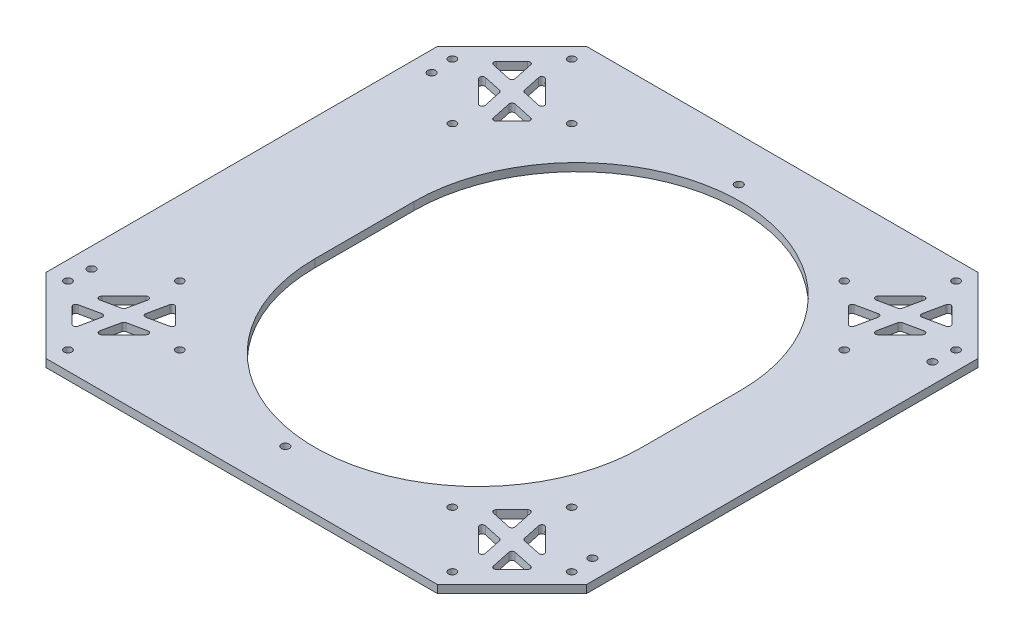
SolidWorks part; units mm, degrees
material "Thornel Mat VMA"
ref_plane "前视基准面" through (0, 0, 0) normal (0, 0, 1) x (1, 0, 0)
ref_plane "上视基准面" through (0, 0, 0) normal (0, 1, 0) x (1, 0, 0)
ref_plane "右视基准面" through (0, 0, 0) normal (1, 0, 0) x (0, 0, -1)
sketch "草图1" plane through (0, 0, 0) normal (0, 1, 0) x (1, 0, 0)
  line L0 (-74.2462, 102.5305) -> (-102.5305, 74.2462)
  line L1 (74.2462, 102.5305) -> (-74.2462, 102.5305)
  line L2 (102.5305, 74.2462) -> (102.5305, -74.2462)
  line L3 (74.2462, -102.5305) -> (-74.2462, -102.5305)
  line L4 (-102.5305, 74.2462) -> (-102.5305, -74.2462)
  line L5 (102.5305, 102.5305) -> (-102.5305, -102.5305) construction
  line L6 (102.5305, -102.5305) -> (-102.5305, 102.5305) construction
  line L7 (102.5305, -74.2462) -> (74.2462, -102.5305)
  line L8 (-102.5305, -74.2462) -> (-74.2462, -102.5305)
  line L9 (74.2462, 102.5305) -> (102.5305, 74.2462)
  line L10 (-102.5305, 102.5305) -> (-102.5305, -102.5305) construction
  line L11 (-102.5305, -102.5305) -> (102.5305, -102.5305) construction
  line L12 (102.5305, -102.5305) -> (102.5305, 102.5305) construction
  line L13 (102.5305, 102.5305) -> (-102.5305, 102.5305) construction
  point P0 (0, 0)
  dimension "D1" = 250
  dimension "D2" = 40
extrude "凸台-拉伸1" add sketch "草图1" along normal blind 3
hole_wizard "孔1" positions "草图4" profile "草图5" legacy
sketch "草图4" plane through (0, 3, 0) normal (0, 1, 0) x (1, 0, 0)
  point P0 (-95.5397, 72.9159)
  point P3 (-74.3265, 51.7027)
  point P6 (-51.6991, 74.3301)
  point P9 (-72.9123, 95.5433)
  point P16 (72.9159, 95.5397)
  point P17 (51.7027, 74.3265)
  point P18 (74.3301, 51.6991)
  point P19 (95.5433, 72.9123)
  point P20 (95.5397, -72.9159)
  point P21 (74.3265, -51.7027)
  point P22 (51.6991, -74.3301)
  point P23 (72.9123, -95.5433)
  point P24 (-72.9159, -95.5397)
  point P25 (-51.7027, -74.3265)
  point P26 (-74.3301, -51.6991)
  point P27 (-95.5433, -72.9123)
  dimension "D1" = 4
sketch "草图5" plane through (-95.5397, 3, -72.9159) normal (1, 0, 0) x (0, 0, 1)
  line L0 (0, 0) -> (0, 100)
  line L1 (0, 100) -> (1.45, 100)
  line L2 (1.45, 100) -> (1.45, 0)
  line L3 (1.45, 0) -> (0, 0)
  line L4 (0, 110) -> (0, -10) construction
  dimension "直径" = 2.9
  dimension "深度" = 100
sketch "草图7" plane through (0, 3, 0) normal (0, 1, 0) x (1, 0, 0)
  line L0 (-95.5397, 72.9159) -> (-51.6991, 74.3301) construction
  line L1 (-86.393, 80.4842) -> (-80.4806, 86.3966)
  line L2 (-84.1601, 71.4358) -> (-75.8066, 63.0823)
  line L3 (-71.4322, 84.1637) -> (-63.0787, 75.8102)
  line L4 (-66.7582, 60.8494) -> (-60.8458, 66.7618)
  line L5 (-89.8008, 77.0764) -> (-57.438, 70.1696) construction
  line L6 (-77.0728, 89.8044) -> (-70.166, 57.4416) construction
  line L7 (-49.2242, 67.6126) -> (-79.6109, 97.9993) construction
  line L8 (-74.2462, 102.5305) -> (-102.5305, 74.2462) construction
  line L9 (-85.8946, 78.7991) -> (-78.378, 77.1949)
  line L10 (-83.2443, 73.1208) -> (-76.36, 71.6516)
  line L11 (-87.6941, 79.1831) -> (-89.8008, 77.0764) construction
  line L12 (-89.8008, 77.0764) -> (-86.5509, 73.8265) construction
  line L13 (-60.6879, 73.4195) -> (-57.438, 70.1696) construction
  line L14 (-57.438, 70.1696) -> (-59.5447, 68.0629) construction
  line L15 (-67.4604, 74.8648) -> (-68.504, 69.975) construction
  line L16 (-73.6194, 73.623) -> (-67.2554, 79.987) construction
  line L17 (-74.1216, 63.9981) -> (-75.5908, 70.8824)
  line L18 (-68.4433, 61.3478) -> (-70.0475, 68.8644)
  line L19 (-70.8788, 75.5944) -> (-63.9945, 74.1252)
  line L20 (-77.1913, 78.3816) -> (-78.7955, 85.8982)
  line L21 (-68.8608, 70.0511) -> (-61.3442, 68.4469)
  line L22 (-71.648, 76.3636) -> (-73.1172, 83.2479)
  line L23 (80.4842, 86.393) -> (86.3966, 80.4806)
  line L24 (71.4358, 84.1601) -> (63.0823, 75.8066)
  line L25 (84.1637, 71.4322) -> (75.8102, 63.0787)
  line L26 (60.8494, 66.7582) -> (66.7618, 60.8458)
  line L27 (78.7991, 85.8946) -> (77.1949, 78.378)
  line L28 (73.1208, 83.2443) -> (71.6516, 76.36)
  line L29 (63.9981, 74.1216) -> (70.8824, 75.5908)
  line L30 (61.3478, 68.4433) -> (68.8644, 70.0475)
  line L31 (75.5944, 70.8788) -> (74.1252, 63.9945)
  line L32 (78.3816, 77.1913) -> (85.8982, 78.7955)
  line L33 (70.0511, 68.8608) -> (68.4469, 61.3442)
  line L34 (76.3636, 71.648) -> (83.2479, 73.1172)
  line L35 (72.9159, 95.5397) -> (74.3301, 51.6991) construction
  line L36 (77.0764, 89.8008) -> (70.1696, 57.438) construction
  line L37 (89.8044, 77.0728) -> (57.4416, 70.166) construction
  line L38 (79.1831, 87.6941) -> (77.0764, 89.8008) construction
  line L39 (77.0764, 89.8008) -> (73.8265, 86.5509) construction
  line L40 (73.4195, 60.6879) -> (70.1696, 57.438) construction
  line L41 (70.1696, 57.438) -> (68.0629, 59.5447) construction
  line L42 (74.8648, 67.4604) -> (69.975, 68.504) construction
  line L43 (73.623, 73.6194) -> (79.987, 67.2554) construction
  line L44 (86.393, -80.4842) -> (80.4806, -86.3966)
  line L45 (84.1601, -71.4358) -> (75.8066, -63.0823)
  line L46 (71.4322, -84.1637) -> (63.0787, -75.8102)
  line L47 (66.7582, -60.8494) -> (60.8458, -66.7618)
  line L48 (85.8946, -78.7991) -> (78.378, -77.1949)
  line L49 (83.2443, -73.1208) -> (76.36, -71.6516)
  line L50 (74.1216, -63.9981) -> (75.5908, -70.8824)
  line L51 (68.4433, -61.3478) -> (70.0475, -68.8644)
  line L52 (70.8788, -75.5944) -> (63.9945, -74.1252)
  line L53 (77.1913, -78.3816) -> (78.7955, -85.8982)
  line L54 (68.8608, -70.0511) -> (61.3442, -68.4469)
  line L55 (71.648, -76.3636) -> (73.1172, -83.2479)
  line L56 (95.5397, -72.9159) -> (51.6991, -74.3301) construction
  line L57 (89.8008, -77.0764) -> (57.438, -70.1696) construction
  line L58 (77.0728, -89.8044) -> (70.166, -57.4416) construction
  line L59 (87.6941, -79.1831) -> (89.8008, -77.0764) construction
  line L60 (89.8008, -77.0764) -> (86.5509, -73.8265) construction
  line L61 (60.6879, -73.4195) -> (57.438, -70.1696) construction
  line L62 (57.438, -70.1696) -> (59.5447, -68.0629) construction
  line L63 (67.4604, -74.8648) -> (68.504, -69.975) construction
  line L64 (73.6194, -73.623) -> (67.2554, -79.987) construction
  line L65 (-80.4842, -86.393) -> (-86.3966, -80.4806)
  line L66 (-71.4358, -84.1601) -> (-63.0823, -75.8066)
  line L67 (-84.1637, -71.4322) -> (-75.8102, -63.0787)
  line L68 (-60.8494, -66.7582) -> (-66.7618, -60.8458)
  line L69 (-78.7991, -85.8946) -> (-77.1949, -78.378)
  line L70 (-73.1208, -83.2443) -> (-71.6516, -76.36)
  line L71 (-63.9981, -74.1216) -> (-70.8824, -75.5908)
  line L72 (-61.3478, -68.4433) -> (-68.8644, -70.0475)
  line L73 (-75.5944, -70.8788) -> (-74.1252, -63.9945)
  line L74 (-78.3816, -77.1913) -> (-85.8982, -78.7955)
  line L75 (-70.0511, -68.8608) -> (-68.4469, -61.3442)
  line L76 (-76.3636, -71.648) -> (-83.2479, -73.1172)
  line L77 (-72.9159, -95.5397) -> (-74.3301, -51.6991) construction
  line L78 (-77.0764, -89.8008) -> (-70.1696, -57.438) construction
  line L79 (-89.8044, -77.0728) -> (-57.4416, -70.166) construction
  line L80 (-79.1831, -87.6941) -> (-77.0764, -89.8008) construction
  line L81 (-77.0764, -89.8008) -> (-73.8265, -86.5509) construction
  line L82 (-73.4195, -60.6879) -> (-70.1696, -57.438) construction
  line L83 (-70.1696, -57.438) -> (-68.0629, -59.5447) construction
  line L84 (-74.8648, -67.4604) -> (-69.975, -68.504) construction
  line L85 (-73.623, -73.6194) -> (-79.987, -67.2554) construction
  arc A0 (-63.0787, 75.8102) -> (-63.9945, 74.1252) centre (-63.7858, 75.1031) cw
  arc A1 (-70.8788, 75.5944) -> (-71.648, 76.3636) centre (-70.67, 76.5724) cw
  arc A2 (-71.4322, 84.1637) -> (-73.1172, 83.2479) centre (-72.1393, 83.4566) ccw
  arc A3 (-78.7955, 85.8982) -> (-80.4806, 86.3966) centre (-79.7735, 85.6895) ccw
  arc A4 (-85.8946, 78.7991) -> (-86.393, 80.4842) centre (-85.6859, 79.7771) cw
  arc A5 (-78.378, 77.1949) -> (-77.1913, 78.3816) centre (-78.1693, 78.1729) ccw
  arc A6 (-66.7582, 60.8494) -> (-68.4433, 61.3478) centre (-67.4653, 61.5565) cw
  arc A7 (-60.8458, 66.7618) -> (-61.3442, 68.4469) centre (-61.5529, 67.4689) ccw
  arc A8 (-68.8608, 70.0511) -> (-70.0475, 68.8644) centre (-69.0695, 69.0731) ccw
  arc A9 (-75.8066, 63.0823) -> (-74.1216, 63.9981) centre (-75.0995, 63.7894) ccw
  arc A10 (-75.5908, 70.8824) -> (-76.36, 71.6516) centre (-76.5688, 70.6736) ccw
  arc A11 (-83.2443, 73.1208) -> (-84.1601, 71.4358) centre (-83.453, 72.1429) ccw
  arc A12 (75.8102, 63.0787) -> (74.1252, 63.9945) centre (75.1031, 63.7858) cw
  arc A13 (75.5944, 70.8788) -> (76.3636, 71.648) centre (76.5724, 70.67) cw
  arc A14 (84.1637, 71.4322) -> (83.2479, 73.1172) centre (83.4566, 72.1393) ccw
  arc A15 (85.8982, 78.7955) -> (86.3966, 80.4806) centre (85.6895, 79.7735) ccw
  arc A16 (78.7991, 85.8946) -> (80.4842, 86.393) centre (79.7771, 85.6859) cw
  arc A17 (77.1949, 78.378) -> (78.3816, 77.1913) centre (78.1729, 78.1693) ccw
  arc A18 (60.8494, 66.7582) -> (61.3478, 68.4433) centre (61.5565, 67.4653) cw
  arc A19 (66.7618, 60.8458) -> (68.4469, 61.3442) centre (67.4689, 61.5529) ccw
  arc A20 (70.0511, 68.8608) -> (68.8644, 70.0475) centre (69.0731, 69.0695) ccw
  arc A21 (63.0823, 75.8066) -> (63.9981, 74.1216) centre (63.7894, 75.0995) ccw
  arc A22 (70.8824, 75.5908) -> (71.6516, 76.36) centre (70.6736, 76.5688) ccw
  arc A23 (73.1208, 83.2443) -> (71.4358, 84.1601) centre (72.1429, 83.453) ccw
  arc A24 (63.0787, -75.8102) -> (63.9945, -74.1252) centre (63.7858, -75.1031) cw
  arc A25 (70.8788, -75.5944) -> (71.648, -76.3636) centre (70.67, -76.5724) cw
  arc A26 (71.4322, -84.1637) -> (73.1172, -83.2479) centre (72.1393, -83.4566) ccw
  arc A27 (78.7955, -85.8982) -> (80.4806, -86.3966) centre (79.7735, -85.6895) ccw
  arc A28 (85.8946, -78.7991) -> (86.393, -80.4842) centre (85.6859, -79.7771) cw
  arc A29 (78.378, -77.1949) -> (77.1913, -78.3816) centre (78.1693, -78.1729) ccw
  arc A30 (66.7582, -60.8494) -> (68.4433, -61.3478) centre (67.4653, -61.5565) cw
  arc A31 (60.8458, -66.7618) -> (61.3442, -68.4469) centre (61.5529, -67.4689) ccw
  arc A32 (68.8608, -70.0511) -> (70.0475, -68.8644) centre (69.0695, -69.0731) ccw
  arc A33 (75.8066, -63.0823) -> (74.1216, -63.9981) centre (75.0995, -63.7894) ccw
  arc A34 (75.5908, -70.8824) -> (76.36, -71.6516) centre (76.5688, -70.6736) ccw
  arc A35 (83.2443, -73.1208) -> (84.1601, -71.4358) centre (83.453, -72.1429) ccw
  arc A36 (-75.8102, -63.0787) -> (-74.1252, -63.9945) centre (-75.1031, -63.7858) cw
  arc A37 (-75.5944, -70.8788) -> (-76.3636, -71.648) centre (-76.5724, -70.67) cw
  arc A38 (-84.1637, -71.4322) -> (-83.2479, -73.1172) centre (-83.4566, -72.1393) ccw
  arc A39 (-85.8982, -78.7955) -> (-86.3966, -80.4806) centre (-85.6895, -79.7735) ccw
  arc A40 (-78.7991, -85.8946) -> (-80.4842, -86.393) centre (-79.7771, -85.6859) cw
  arc A41 (-77.1949, -78.378) -> (-78.3816, -77.1913) centre (-78.1729, -78.1693) ccw
  arc A42 (-60.8494, -66.7582) -> (-61.3478, -68.4433) centre (-61.5565, -67.4653) cw
  arc A43 (-66.7618, -60.8458) -> (-68.4469, -61.3442) centre (-67.4689, -61.5529) ccw
  arc A44 (-70.0511, -68.8608) -> (-68.8644, -70.0475) centre (-69.0731, -69.0695) ccw
  arc A45 (-63.0823, -75.8066) -> (-63.9981, -74.1216) centre (-63.7894, -75.0995) ccw
  arc A46 (-70.8824, -75.5908) -> (-71.6516, -76.36) centre (-70.6736, -76.5688) ccw
  arc A47 (-73.1208, -83.2443) -> (-71.4358, -84.1601) centre (-72.1429, -83.453) ccw
  point P5 (-73.6194, 73.623)
  point P14 (-72.9123, 95.5433)
  point P21 (-67.9822, 72.4199)
  point P38 (-71.5127, 75.7297)
  point P41 (-73.8229, 86.5545)
  point P44 (-79.1795, 87.6977)
  point P50 (-76.8693, 76.8729)
  point P53 (-68.0593, 59.5483)
  point P59 (-70.3695, 70.3731)
  point P62 (-73.4159, 60.6915)
  point P73 (73.623, 73.6194)
  point P84 (72.4199, 67.9822)
  point P126 (73.6194, -73.623)
  point P137 (67.9822, -72.4199)
  point P179 (-73.623, -73.6194)
  point P190 (-72.4199, -67.9822)
  point P230 (0, 0)
  dimension "D4" = 1
  dimension "D1" = 7
  dimension "D2" = 7
  dimension "D3" = 5
  dimension "D5" = 4
extrude "切除-拉伸2" cut sketch "草图7" against normal through all both and the other way through all
sketch "草图8" plane through (0, 3, 0) normal (0, 1, 0) x (1, 0, 0)
  line L0 (-208.5651, 0) -> (0, 0) construction
  line L1 (-102.5305, -74.2462) -> (-50.5427, 0) construction
  line L3 (0, 0) -> (-88.3883, -88.3883) construction
  line L4 (-102.5305, -74.2462) -> (-74.2462, -102.5305) construction
  line L5 (0, 102.5305) -> (0, -102.5305) construction
  line L6 (74.2462, 102.5305) -> (-74.2462, 102.5305) construction
  line L7 (-74.2462, -102.5305) -> (74.2462, -102.5305) construction
  circle A0 centre (-208.5651, 0) radius 129.4443
  circle A2 centre (0, 208.5651) radius 129.4443
  circle A3 centre (208.5651, 0) radius 129.4443
  circle A4 centre (0, -208.5651) radius 129.4443
  point P28 (0, 0)
  dimension "D1" = 10
  dimension "D2" = 4
extrude "切除-拉伸3" cut sketch "草图8" against normal through all both and the other way through all
sketch "草图11" plane through (0, 3, 0) normal (0, 1, 0) x (1, 0, 0)
  line L0 (5.9793, 0) -> (0, 0) construction
  circle A0 centre (5.9793, 0) radius 60
  point P2 (0, 0)
  point P3 (-54.0207, 0)
  point P5 (0, 0)
  dimension "D1" = 120
extrude "切除-拉伸6" cut sketch "草图11" against normal through all both and the other way through all
sketch "草图15" plane through (0, 3, 0) normal (0, 1, 0) x (1, 0, 0)
  line L0 (41.391, -82.1632) -> (51.3964, -89.7617)
  line L1 (-42.4295, 81.6317) -> (-54.3839, 91.0992)
  line L2 (41.391, 82.1632) -> (34.5498, 61.2743)
  line L3 (-42.4295, -81.6317) -> (-34.5316, -61.2845)
  line L4 (41.391, -82.1632) -> (34.5498, -61.2743)
  line L5 (-42.4295, -81.6317) -> (-54.3839, -91.0992)
  line L6 (0, 0) -> (-131.4894, 0) construction
  line L7 (-42.4295, 81.6317) -> (-34.5316, 61.2845)
  line L8 (41.391, 82.1632) -> (51.3964, 89.7617)
  arc A0 (-33.444, -85.7059) -> (-5.8723, -91.8124) centre (0, 0) ccw
  arc A1 (33.444, 85.7059) -> (40.1835, 85.5158) centre (37.0792, 95.0218) ccw
  arc A2 (-34.5316, -61.2845) -> (34.5498, -61.2743) centre (0, 0) ccw
  arc A3 (-40.1835, 85.5158) -> (-33.444, 85.7059) centre (-37.0792, 95.0218) ccw
  arc A4 (-40.1835, 85.5158) -> (-54.3839, 91.0992) centre (0, 208.5651) cw
  arc A5 (51.3964, -89.7617) -> (40.1835, -85.5158) centre (0, -208.5651) ccw
  arc A6 (74.2462, -102.5305) -> (-74.2462, -102.5305) centre (0, -208.5651) ccw construction
  arc A7 (-5.8723, -91.8124) -> (33.444, -85.7059) centre (0, 0) ccw
  arc A8 (-40.1835, -85.5158) -> (-54.3839, -91.0992) centre (0, -208.5651) ccw
  arc A9 (-40.1835, -85.5158) -> (-33.444, -85.7059) centre (-37.0792, -95.0218) cw
  arc A10 (33.444, -85.7059) -> (40.1835, -85.5158) centre (37.0792, -95.0218) cw
  arc A11 (-5.8723, 91.8124) -> (33.444, 85.7059) centre (0, 0) cw
  arc A12 (51.3964, 89.7617) -> (40.1835, 85.5158) centre (0, 208.5651) cw
  arc A13 (-34.5316, 61.2845) -> (34.5498, 61.2743) centre (0, 0) cw
  arc A14 (-33.444, 85.7059) -> (-5.8723, 91.8124) centre (0, 0) cw
  point P22 (-36.605, -84.4042)
  point P35 (-36.605, 84.4042)
  dimension "D2" = 10
extrude "凸台-拉伸3" add sketch "草图15" against normal up to surface (3 mm away) up to face at (5.9793, 0, 60)
sketch "草图18" plane through (0, 3, 0) normal (0, 1, 0) x (1, 0, 0)
  line L0 (-56.0207, 0) -> (5.9793, 0) construction
  line L1 (5.9793, 18.75) -> (5.9793, -18.75) construction
  line L2 (67.9793, 18.75) -> (67.9793, -18.75)
  line L3 (-56.0207, 18.75) -> (-56.0207, -18.75)
  arc A1 (67.9793, 18.75) -> (-56.0207, 18.75) centre (5.9793, 18.75) ccw
  arc A2 (-56.0207, -18.75) -> (67.9793, -18.75) centre (5.9793, -18.75) ccw
  circle A3 centre (5.9793, 0) radius 60 construction
  point P0 (-56.0207, 0)
  point P1 (-54.0207, 0)
  point P5 (11.4315, 0)
  point P8 (5.9793, 0)
  dimension "D1" = 62
  dimension "D2" = 2
  dimension "D3" = 37.5
extrude "切除-拉伸7" cut sketch "草图18" against normal through all both and the other way through all
sketch "草图26" plane through (0, 3, 0) normal (0, 1, 0) x (1, 0, 0)
  line L0 (0, 92) -> (56.2887, 92)
  line L1 (0, 0) -> (48.0918, 0) construction
  line L2 (56.2887, 84.4086) -> (0, 84.4086)
  line L3 (0, 84.4086) -> (0, 92)
  line L4 (66.8384, 97.7118) -> (56.2887, 84.4086)
  line L5 (66.8384, -97.7118) -> (56.2887, -84.4086)
  line L6 (0, -84.4086) -> (0, -92)
  line L7 (56.2887, -84.4086) -> (0, -84.4086)
  line L8 (0, -92) -> (56.2887, -92)
  arc A0 (33.444, 85.7059) -> (-33.444, 85.7059) centre (0, 0) ccw construction
  arc A1 (40.1835, 85.5158) -> (74.2462, 102.5305) centre (0, 208.5651) ccw construction
  arc A2 (56.2887, 92) -> (66.8384, 97.7118) centre (0, 208.5651) ccw
  arc A3 (56.2887, -92) -> (66.8384, -97.7118) centre (0, -208.5651) cw
extrude "凸台-拉伸6" add sketch "草图26" against normal up to surface (3 mm away) up to face at (5.9793, 0, 0)
hole_wizard "孔3" positions "草图30" profile "草图31" legacy end condition through all
sketch "草图30" plane through (0, 0, 0) normal (0, -1, 0) x (-1, 0, 0)
  line L0 (0, -86) -> (0, 86) construction
  line L2 (0, 92) -> (-56.2887, 92) construction
  point P0 (0, 0)
  point P11 (0, -86)
  point P14 (0, 86)
  dimension "D1" = 6
sketch "草图31" plane through (0, 0, 0) normal (1, 0, 0) x (0, 0, -1)
  line L0 (0, 0) -> (0, 3)
  line L1 (0, 3) -> (1.5, 3)
  line L2 (1.5, 3) -> (1.5, 0)
  line L3 (1.5, 0) -> (0, 0)
  line L4 (0, 110) -> (0, -10) construction
  dimension "直径" = 3
  dimension "深度" = 3
sketch "草图32" plane through (0, 3, 0) normal (0, 1, 0) x (1, 0, 0)
  line L0 (-74.2462, -102.5305) -> (74.2462, -102.5305)
  line L1 (74.2462, -102.5305) -> (58.9058, -89.2362)
  line L2 (58.9058, -89.2362) -> (-12.8602, -89.2362)
  line L3 (-12.8602, -89.2362) -> (-37.5552, -80.4515)
  line L4 (-37.5552, -80.4515) -> (-66.233, -94.0798)
  line L5 (-66.233, -94.0798) -> (-74.2462, -102.5305)
  line L6 (-79.1207, 0) -> (79.1207, 0) construction
  line L7 (-66.233, 94.0798) -> (-74.2462, 102.5305)
  line L8 (-37.5552, 80.4515) -> (-66.233, 94.0798)
  line L9 (-12.8602, 89.2362) -> (-37.5552, 80.4515)
  line L10 (58.9058, 89.2362) -> (-12.8602, 89.2362)
  line L11 (74.2462, 102.5305) -> (58.9058, 89.2362)
  line L12 (-74.2462, 102.5305) -> (74.2462, 102.5305)
  line L13 (-102.5305, 74.2462) -> (-102.5305, -74.2462)
  line L14 (-102.5305, -74.2462) -> (-89.5834, -61.2991)
  line L15 (-89.5834, -61.2991) -> (-74.7652, 0)
  line L16 (-74.7652, 0) -> (-89.5834, 64.0658)
  line L17 (-89.5834, 64.0658) -> (-102.5305, 74.2462)
  line L18 (102.5305, 74.2462) -> (102.5305, -74.2462)
  line L19 (102.5305, -74.2462) -> (84.9729, -53.4914)
  line L20 (84.9729, -53.4914) -> (72.6017, 0)
  line L21 (72.6017, 0) -> (87.9714, 60.2156)
  line L22 (87.9714, 60.2156) -> (102.5305, 74.2462)
  arc A0 (-102.5305, -74.2462) -> (-102.5305, 74.2462) centre (-208.5651, 0) ccw construction
  arc A1 (102.5305, 74.2462) -> (102.5305, -74.2462) centre (208.5651, 0) ccw construction
extrude "凸台-拉伸9" add sketch "草图32" against normal up to surface (3 mm away) up to face at (0, 0, 84.5)
sketch "草图19" plane through (0, 3, 0) normal (0, 1, 0) x (1, 0, 0)
  line L1 (95, 64.5) -> (-95, 64.5)
  line L2 (95, 64.5) -> (95, -64.5)
  line L3 (95, -64.5) -> (-95, -64.5)
  line L4 (-95, 64.5) -> (-95, -64.5)
  line L5 (95, 64.5) -> (-95, -64.5) construction
  line L6 (95, -64.5) -> (-95, 64.5) construction
  point P5 (0, 0)
  point P8 (0, 0)
  point P9 (0, 0)
  dimension "D1" = 129
  dimension "D2" = 190
hole_wizard "孔2" positions "草图20" profile "草图21" legacy end condition through all
sketch "草图20" plane through (0, 3, 0) normal (0, 1, 0) x (1, 0, 0)
  point P0 (-95, 64.5)
  point P3 (95, 64.5)
  point P6 (-95, -64.5)
  point P9 (95, -64.5)
sketch "草图21" plane through (-95, 3, -64.5) normal (1, 0, 0) x (0, 0, 1)
  line L0 (0, 0) -> (0, 3)
  line L1 (0, 3) -> (1.5, 3)
  line L2 (1.5, 3) -> (1.5, 0)
  line L3 (1.5, 0) -> (0, 0)
  line L4 (0, 110) -> (0, -10) construction
  dimension "直径" = 3
  dimension "深度" = 3
